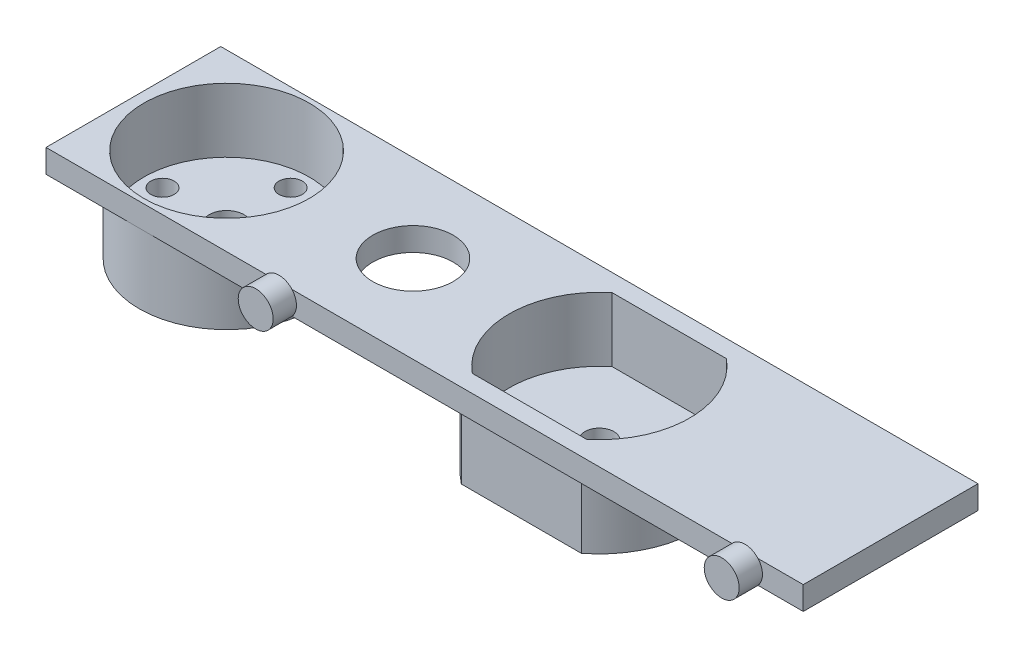
SolidWorks part; units mm, degrees
ref_plane "前视基准面" through (0, 0, 0) normal (0, 0, 1) x (1, 0, 0)
ref_plane "上视基准面" through (0, 0, 0) normal (0, 1, 0) x (1, 0, 0)
ref_plane "右视基准面" through (0, 0, 0) normal (1, 0, 0) x (0, 0, -1)
other "Configuration Table"
sketch "草图1" plane through (0, 0, 0) normal (0, 1, 0) x (1, 0, 0)
  line L0 (0, 7.5) -> (0, -7.5) construction
  line L1 (-25, 7.5) -> (25, 7.5)
  line L2 (-25, 7.5) -> (-25, -7.5)
  line L3 (-25, -7.5) -> (25, -7.5)
  line L4 (25, 7.5) -> (25, -7.5)
  line L5 (-25, 0) -> (25, 0) construction
  line L7 (-25, -7.5) -> (-40, -7.5)
  line L10 (-25, -7.5) -> (-25, 7.5)
  line L11 (-25, 7.5) -> (-40, 7.5)
  line L12 (-40, -7.5) -> (-40, 7.5)
  line L14 (-25, 7.5) -> (-40, 7.5)
  dimension "D1" = 50
  dimension "D2" = 15
  dimension "D6" = 15
  dimension "D7" = 15
extrude "凸台-拉伸1" add sketch "草图1" along normal blind 2 contours L11 L2 | L2 L1 L4 L3 | L10 L7 L12 L11 region at (-32.5, 0, 0)
sketch "草图2" plane through (0, 0, 0) normal (0, 1, 0) x (1, 0, 0)
  line L0 (0, 7.5) -> (0, -7.5) construction
  line L1 (25, 7.5) -> (-40, 7.5) construction
  line L2 (-32, 7.5) -> (-32, -7.5) construction
  line L3 (-40, -7.5) -> (-40, 7.5) construction
  line L4 (-25, 7.5) -> (-25, -7.5) construction
  line L6 (-25, -7.5) -> (25, -7.5) construction
  line L10 (-40, 0) -> (-25, 0) construction
  line L14 (-40, -7.5) -> (25, -7.5) construction
  circle A2 centre (0, 0) radius 1.25
  circle A3 centre (16, 0) radius 4.1
  circle A4 centre (16, 0) radius 3.45
  circle A5 centre (-16, 0) radius 4.1
  circle A6 centre (-16, 0) radius 3.45
  circle A8 centre (24, 0) radius 1.25
  circle A9 centre (-24, 0) radius 1.25
  circle A11 centre (-32, 0) radius 1.5
  circle A12 centre (-26.5, 0) radius 1
  circle A13 centre (-32, -5.5) radius 1
  circle A14 centre (-37.5, 0) radius 1
  circle A15 centre (-32, 5.5) radius 1
  point P10 (-20.8007, -1.78)
  point P11 (-26.0369, 2.6693)
  point P36 (0, -7.5)
  dimension "D3" = 2.5
  dimension "D4" = 6.9
  dimension "D5" = 8.2
  dimension "D7" = 15
  dimension "D8" = 2.5
  dimension "D11" = 3
  dimension "D12" = 2
  dimension "D2" = 8
  dimension "D6" = 16
  dimension "D9" = 16
  dimension "D10" = 8
  dimension "D13" = 5.5
  dimension "D15" = 16
  dimension "D17" = 7.5
  dimension "D14" = 4
extrude "切除-拉伸1" cut sketch "草图2" along normal up to surface (2 mm away) contours A2 | A6 | A14 | A11 | A13 | A12 | A15 up to face at (-7.5, 2, 0)
sketch "草图4" plane through (0, 0, 7.5) normal (0, 0, 1) x (1, 0, 0)
  line L0 (25, 1) -> (-40, 1) construction
  line L1 (25, 2) -> (25, 0) construction
  line L2 (-40, 2) -> (-40, 0) construction
  line L3 (0, 0) -> (0, 2) construction
  line L5 (25, 2) -> (25, 0) construction
  line L6 (-40, 2) -> (25, 2) construction
  circle A0 centre (20, 1) radius 1.5
  circle A1 centre (-20, 1) radius 1.5
  dimension "D1" = 3
  dimension "D2" = 3
  dimension "D3" = 20
  dimension "D4" = 20
  dimension "D5" = 25
extrude "凸台-拉伸2" add sketch "草图4" along normal blind 2
sketch "草图5" plane through (0, 2, 0) normal (0, 1, 0) x (1, 0, 0)
  line L0 (0, 0) -> (0, 4.126) construction
  line L1 (4.9054, -6) -> (-4.9054, -6)
  line L2 (-4.7026, 0) -> (-2.9861, 0) construction
  line L3 (4.9054, 6) -> (-4.9054, 6)
  line L4 (5.149, -6.7) -> (-5.149, -6.7)
  line L5 (5.149, 6.7) -> (-5.149, 6.7)
  arc A0 (-4.9054, 6) -> (-4.9054, -6) centre (0, 0) ccw
  arc A1 (4.9054, -6) -> (4.9054, 6) centre (0, 0) ccw
  arc A2 (-5.149, 6.7) -> (-5.149, -6.7) centre (0, 0) ccw
  arc A3 (5.149, -6.7) -> (5.149, 6.7) centre (0, 0) ccw
  circle A4 centre (-32, 0) radius 7.1
  circle A5 centre (-32, 0) radius 7.5
  point P14 (0, -6)
  point P15 (0, 6)
  point P21 (0, -6.7)
  point P22 (0, 6.7)
  circle M2 centre (-32, 5.5) radius 1
  circle M3 centre (-37.5, 0) radius 1
  circle M4 centre (-32, 0) radius 1.5
  circle M5 centre (-32, -5.5) radius 1
  circle M6 centre (-26.5, 0) radius 1
  circle M9 centre (0, 0) radius 1.25
  dimension "D1" = 15.5
  dimension "D3" = 16.9
  dimension "D5" = 14.2
  dimension "D6" = 15
  dimension "D2" = 12
  dimension "D4" = 13.4
extrude "凸台-拉伸3" add sketch "草图5" against normal blind 8
extrude "凸台-拉伸4" add sketch "草图5<5>" against normal up to surface (8 mm away) contours L1 A1 L3 A0 M9 | A4 M2 M3 M4 M6 M5 region at (0, 2, 5.804) region at (-38.8992, 2, 0) up to face at (0, -6, 0)
sketch "草图5<5>" plane through (0, 2, 0) normal (0, 1, 0) x (1, 0, 0) same geometry as "草图5"
extrude "切除-拉伸3" cut sketch "草图5<6>" against normal offset from surface (5.5 mm away) 2.5 contours L1 A1 L3 A0 M9 | A4 region at (0, 2, 5.804) up to face at (0, -6, 0)
sketch "草图5<6>" plane through (0, 2, 0) normal (0, 1, 0) x (1, 0, 0) same geometry as "草图5"
